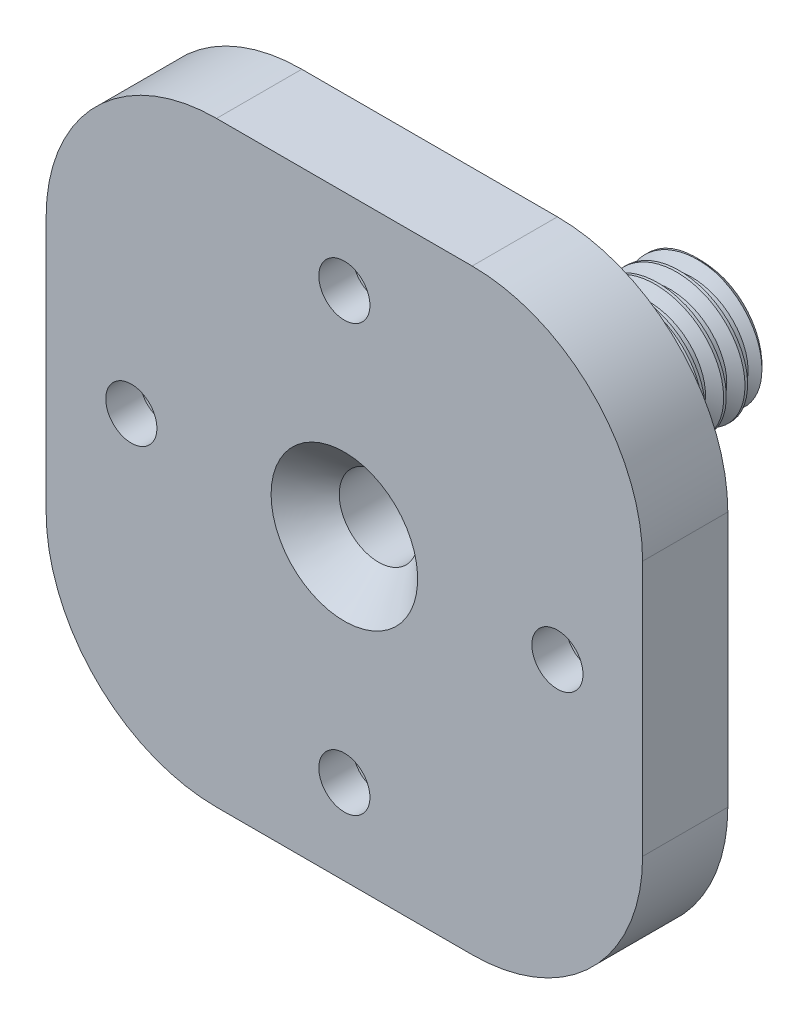
SolidWorks part; units mm, degrees
ref_plane "Alzado" through (0, 0, 0) normal (0, 0, 1) x (1, 0, 0)
ref_plane "Planta" through (0, 0, 0) normal (0, 1, 0) x (1, 0, 0)
ref_plane "Vista lateral" through (0, 0, 0) normal (1, 0, 0) x (0, 0, -1)
sketch "Croquis1" plane through (0, 0, 0) normal (0, 0, 1) x (1, 0, 0)
  circle A0 centre (0, 0) radius 3.9
  circle A23 centre (-0.4495, 0.5219) radius 0.5
  circle A24 centre (0.6209, 0.3005) radius 0.5
  circle A30 centre (0.707, 1.5431) radius 0.5
  circle A37 centre (-0.4495, 1.6293) radius 0.5
  circle A38 centre (-1.4584, 0.9649) radius 0.5
  circle A39 centre (1.6298, 0.8461) radius 0.5
  circle A45 centre (-1.6798, -0.4992) radius 0.5
  circle A46 centre (-0.917, -1.4466) radius 0.5
  circle A47 centre (0.2641, -1.7173) radius 0.5
  circle A48 centre (1.6298, -0.3762) radius 0.5
  circle A96 centre (0, 0) radius 2.3
  dimension "D1" = 7.8
  dimension "D2" = 1.6
extrude "Saliente-Extruir1" add sketch "Croquis1" against normal blind 7 contours A0
chamfer "Chaflán2" distance 0.4 angle 45 1 edges at (3.9, 0, -7)
thread "Rosca1" pitch 1.25 method cut profile "Perfil de rosca1" start angle 0, offset 1.5, length 9, pitch 1.25, diameter 7.8
ref_plane "Plano1" through (3.9, 0, -8.1) normal (0, -1, 0) x (1, 0, 0)
sketch "Perfil de rosca1" plane through (3.9, 0, -8.1) normal (0, -1, 0) x (1, 0, 0)
  line L0 (0, 0) -> (0, 1.25) construction
  line L11 (0, 0) -> (0, 1.0937)
  line L12 (0, 1.0937) -> (-0.6766, 0.7031)
  line L13 (-0.6766, 0.7031) -> (-0.6766, 0.3906)
  line L15 (-0.6766, 0.3906) -> (0, 0)
  line L17 (-0.6766, 0.5469) -> (0, 0.5469) construction
  point P2 (0, 0)
  dimension "Pitch" = 1.25
  dimension "Profile_Angle" = 60
  dimension "Profile_Land" = 0.3125
  dimension "Profile_Height" = 0.6766
sketch "Croquis20" plane through (0, 0, 0) normal (0, 0, 1) x (1, 0, 0)
  circle A0 centre (0, 0) radius 3.95
  dimension "D1" = 7.9
extrude "Saliente-Extruir2" add sketch "Croquis20" along normal blind 7 contours A0
sketch "Croquis21" plane through (0, 0, 7) normal (0, 0, 1) x (1, 0, 0)
  circle A0 centre (0, 0) radius 5.5
  dimension "D1" = 11
extrude "Saliente-Extruir3" add sketch "Croquis21" along normal blind 2
sketch "Croquis23" plane through (0, 0, 9) normal (0, 0, 1) x (1, 0, 0)
  line L0 (-17.5, 0) -> (17.5, 0) construction
  line L1 (-17.5, -17.5) -> (17.5, -17.5)
  line L2 (-17.5, -17.5) -> (-17.5, 17.5)
  line L3 (-17.5, 17.5) -> (17.5, 17.5)
  line L4 (17.5, -17.5) -> (17.5, 17.5)
  line L7 (0, -17.5) -> (0, 17.5) construction
  circle A0 centre (-12.5, 0) radius 1.5
  circle A1 centre (12.5, 0) radius 1.5
  circle A2 centre (0, -12.5) radius 1.5
  circle A3 centre (0, 12.5) radius 1.5
  point P0 (0, 0)
  point P14 (0, 0)
  dimension "D3" = 3
  dimension "D1" = 35
  dimension "D2" = 35
  dimension "D5" = 5
  dimension "D4" = 5
extrude "Saliente-Extruir4" add sketch "Croquis23" along normal blind 5
chamfer "Chaflán3" distance 2 angle 45 1 edges at (5.5, 0, 9)
sketch "Croquis24" plane through (0, 0, 9) normal (0, 0, -1) x (-1, 0, 0)
  circle A0 centre (12.5, 0) radius 3.5
  circle A1 centre (0, -12.5) radius 3.5
  circle A2 centre (-12.5, 0) radius 3.5
  circle A3 centre (0, 12.5) radius 3.5
  dimension "D1" = 7
extrude "Cortar-Extruir2" cut sketch "Croquis24" against normal blind 3
extrude "Cortar-Extruir1" cut sketch "Croquis1<3>" against normal through all both and the other way through all contours A96
sketch "Croquis1<3>" plane through (0, 0, 0) normal (0, 0, 1) x (1, 0, 0) same geometry as "Croquis1"
chamfer "Chaflán4" distance 2 angle 45 1 edges at (2.3, 0, 14)
fillet "Redondeo1" radius 10 4 edges at (-17.5, -17.5, 11.5) (17.5, -17.5, 11.5) (-17.5, 17.5, 11.5) (17.5, 17.5, 11.5)
sketch "Croquis25" plane through (0, 0, 9) normal (0, 0, -1) x (-1, 0, 0)
  circle A0 centre (0, 0) radius 45
  dimension "D1" = 90
equation "\"D1@Croquis1\" = \"dmax\""
equation "\"pitch\"= 1.25"
equation "\"h\"= 0.866 * \"pitch\""
equation "\"dmax\"= 7.8"
equation "\"dpitch\"= \"dmax\" - 0.649519"
equation "\"dmin\"= \"dmax\" - 1.082532"
equation "\"angle_pressure\"= 60"
equation "\"axis_len\"= 7"
equation "\"D1@Saliente-Extruir2\"=\"axis_len\""
equation "\"D1@Croquis21\"=8+3"
equation "\"D2@Croquis23\"=\"D1@Croquis23\""
equation "\"D4@Croquis23\"=\"D5@Croquis23\""
equation "\"D1@Saliente-Extruir4\"=3+2"
